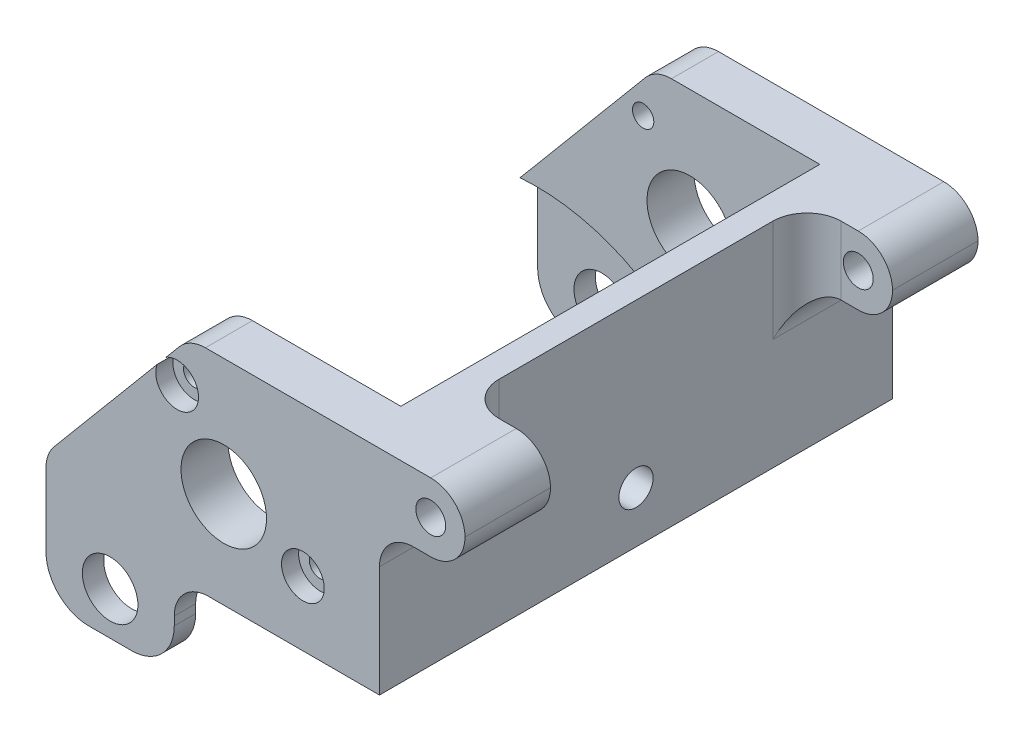
SolidWorks part; units mm, degrees
ref_plane "Front Plane" through (0, 0, 0) normal (0, 0, 1) x (1, 0, 0)
ref_plane "Top Plane" through (0, 0, 0) normal (0, 1, 0) x (1, 0, 0)
ref_plane "Right Plane" through (0, 0, 0) normal (1, 0, 0) x (0, 0, -1)
sketch "Sketch2" plane through (0, 0, 0) normal (0, 0, 1) x (1, 0, 0)
  line L0 (-7.5, 5) -> (-7.5, 15)
  line L1 (-7.5, 15) -> (9.282, 35)
  line L2 (9.282, 35) -> (31.5, 35)
  line L3 (31.5, 35) -> (31.5, 10)
  line L4 (31.5, 10) -> (7.5, 10)
  line L5 (7.5, 10) -> (7.5, 5)
  line L6 (-2.5, 0) -> (2.5, 0)
  line L7 (-7.5, 0) -> (7.5, 0) construction
  line L8 (-7.5, 5) -> (7.5, 5) construction
  line L9 (22.5451, 17.5686) -> (7.8349, 29.594) construction
  line L10 (15.19, 23.5813) -> (13.2912, 21.2586) construction
  line L11 (0, 5) -> (13.2912, 21.2586) construction
  circle A5 centre (0, 5) radius 3.25
  circle A6 centre (22.5451, 17.5686) radius 1.25
  circle A7 centre (7.8349, 29.594) radius 1.25
  circle A8 centre (13.2912, 21.2586) radius 5
  circle A9 centre (15.19, 23.5813) radius 12.5 construction
  arc A10 (2.5, 0) -> (7.5, 5) centre (2.5, 5) ccw
  arc A11 (-7.5, 5) -> (-2.5, 0) centre (-2.5, 5) ccw
  circle A12 centre (0, 5) radius 10 construction
  point P21 (8.7918, 29.4684)
  point P28 (19.6015, 23.9808)
  point P29 (13.1599, 21.3651)
  point P30 (15.7707, 23.091)
  point P31 (12.9824, 21.5063)
  point P32 (13.571, 21.0259)
  point P33 (13.2912, 21.2586)
  dimension "D3" = 6.5
  dimension "D4" = 5
  dimension "D10" = 10
  dimension "D12" = 2.5
  dimension "D14" = 25
  dimension "D15" = 5
  dimension "D16" = 20
  dimension "D1" = 40
  dimension "D2" = 15
  dimension "D5" = 15
  dimension "D6" = 20
  dimension "D7" = 24
  dimension "D8" = 10
  dimension "D9" = 19
  dimension "D11" = 3
  dimension "D13" = 21
extrude "Boss-Extrude1" add sketch "Sketch2" along normal blind 30 and the other way blind 30
sketch "Sketch3" plane through (0, 35, 0) normal (0, 1, 0) x (1, 0, 0)
  line L0 (-7.5, -30) -> (-7.5, 30) construction
  line L1 (-43.5, -27.5) -> (28.5, -27.5)
  line L2 (-43.5, -27.5) -> (-43.5, 27.5)
  line L3 (-43.5, 27.5) -> (28.5, 27.5)
  line L4 (28.5, -27.5) -> (28.5, 27.5)
  line L5 (-43.5, -27.5) -> (28.5, 27.5) construction
  line L6 (-43.5, 27.5) -> (28.5, -27.5) construction
  line L7 (31.5, 30) -> (9.282, 30) construction
  line L8 (31.5, -30) -> (31.5, 30) construction
  point P0 (-7.5, 0)
  dimension "D1" = 2.5
  dimension "D2" = 3
extrude "Cut-Extrude1" cut sketch "Sketch3" against normal through all
sketch "Sketch4" plane through (31.5, 0, 0) normal (1, 0, 0) x (0, 0, -1)
  line L1 (-30, 35) -> (-20, 35)
  line L2 (-30, 35) -> (-30, 27)
  line L3 (-30, 27) -> (-20, 27)
  line L4 (-20, 35) -> (-20, 27)
  dimension "D1" = 10
  dimension "D2" = 8
extrude "Boss-Extrude2" add sketch "Sketch4" along normal blind 10
fillet "Fillet1" radius 4 2 edges at (41.5, 27, 25) (41.5, 35, 25)
sketch "Sketch5" plane through (0, 0, 20) normal (0, 0, -1) x (-1, 0, 0)
  circle A0 centre (-37.5, 31) radius 1.75
  dimension "D1" = 3.5
extrude "Cut-Extrude2" cut sketch "Sketch5" against normal through all
mirror "Mirror1" about plane through (0, 0, 0) normal (0, 0, 1) of "Cut-Extrude2", "Fillet1", "Boss-Extrude2"
fillet "Fillet2" radius 4 10 edges at (31.5, 31, -20) (31.5, 31, 20) (9.282, 35, -28.75) (7.5, 10, -28.75) (31.5, 27, -25) (31.5, 27, 25) (7.5, 10, 28.75) (9.282, 35, 28.75) (-7.5, 15, 28.75) (-7.5, 15, -28.75)
sketch "Sketch6" plane through (0, 0, -27.5) normal (0, 0, 1) x (1, 0, 0)
  line L7 (28.5, 35) -> (11.1472, 35)
  line L8 (8.083, 33.5712) -> (-6.5642, 16.1153)
  line L9 (-7.5, 13.5441) -> (-7.5, 5)
  line L10 (-2.5, 0) -> (2.5, 0)
  line L11 (7.5, 5) -> (7.5, 6)
  line L12 (11.5, 10) -> (28.5, 10)
  line L13 (28.5, 10) -> (28.5, 35)
  line L14 (28.5, 35) -> (11.1472, 35)
  line L15 (8.083, 33.5712) -> (-6.5642, 16.1153)
  line L19 (11.5, 10) -> (28.5, 10)
  line L20 (28.5, 10) -> (28.5, 35)
  circle A2 centre (22.5451, 17.5686) radius 1.25 construction
  circle A3 centre (13.2912, 21.2586) radius 5 construction
  circle A4 centre (7.8349, 29.594) radius 1.25 construction
  circle A5 centre (22.5451, 17.5686) radius 1.25
  arc A6 (11.1472, 35) -> (8.083, 33.5712) centre (11.1472, 31) ccw
  arc A7 (-6.5642, 16.1153) -> (-7.5, 13.5441) centre (-3.5, 13.5441) ccw
  arc A8 (-7.5, 5) -> (-2.5, 0) centre (-2.5, 5) ccw
  arc A9 (2.5, 0) -> (7.5, 5) centre (2.5, 5) ccw
  arc A10 (11.5, 10) -> (7.5, 6) centre (11.5, 6) ccw
  arc A11 (11.1472, 35) -> (8.083, 33.5712) centre (11.1472, 31) ccw
  circle A16 centre (13.2912, 21.2586) radius 5
  circle A17 centre (7.8349, 29.594) radius 1.25
  circle A18 centre (0, 5) radius 10 construction
  arc A19 (11.5, 10) -> (-6.5642, 16.1153) centre (-4.6335, -7.9195) ccw
  point P8 (-5.8706, 16.9419)
  point P25 (12.6865, 10)
  point P32 (-5.949, 16.8485)
  point P34 (11.5, 10)
  point P35 (-6.5642, 16.1153)
  dimension "D1" = 0
  dimension "D2" = 20
extrude "Boss-Extrude3" add sketch "Sketch6" along normal blind 3
sketch "Sketch7" plane through (0, 0, -30) normal (0, 0, -1) x (-1, 0, 0)
  circle A0 centre (-22.5451, 17.5686) radius 2.5
  circle A1 centre (-7.8349, 29.594) radius 2.5
  dimension "D1" = 5
extrude "Cut-Extrude3" cut sketch "Sketch7" against normal blind 2
mirror "Mirror2" about plane through (0, 0, 0) normal (0, 0, 1) of "Cut-Extrude3", "Boss-Extrude3"
sketch "Sketch8" plane through (28.5, 0, 0) normal (-1, 0, 0) x (0, 0, 1)
  line L0 (0, 16) -> (0, 35) construction
  line L1 (24.5, 35) -> (-24.5, 35) construction
  circle A0 centre (0, 16) radius 2
  dimension "D1" = 4
  dimension "D2" = 19
extrude "Cut-Extrude4" cut sketch "Sketch8" against normal through all
